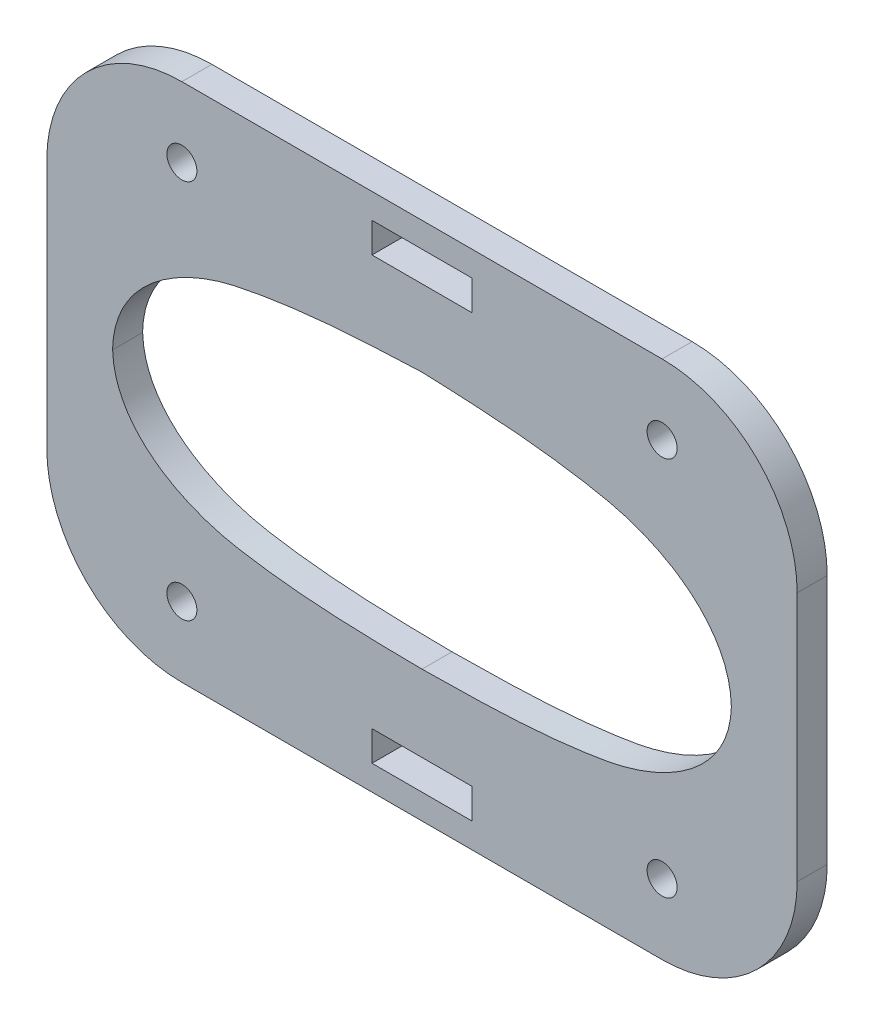
SolidWorks part; units mm, degrees
material "MDF"
ref_plane "Plano frontal" through (0, 0, 0) normal (0, 0, 1) x (1, 0, 0)
ref_plane "Plano superior" through (0, 0, 0) normal (0, 1, 0) x (1, 0, 0)
ref_plane "Plano direito" through (0, 0, 0) normal (1, 0, 0) x (0, 0, -1)
sketch "Esboço1" plane through (0, 0, 0) normal (0, 0, 1) x (1, 0, 0)
  line L0 (37.5, 0.6746) -> (-37.5, 0.6746) construction
  line L5 (24, 26.6746) -> (-24, 26.6746)
  line L6 (37.5, 13.1746) -> (37.5, -11.8254)
  line L7 (24, -25.3254) -> (-24, -25.3254)
  line L8 (-37.5, 13.1746) -> (-37.5, -11.8254)
  line L13 (37.5, 26.6746) -> (-37.5, -25.3254) construction
  line L14 (37.5, -25.3254) -> (-37.5, 26.6746) construction
  line L27 (0, -12.1787) -> (0, 13.528) construction
  line L28 (30.9233, 0) -> (-30.9233, 0) construction
  line L29 (5, -22.8254) -> (-5, -22.8254)
  line L30 (5, -22.8254) -> (5, -19.8254)
  line L31 (5, -19.8254) -> (-5, -19.8254)
  line L32 (-5, -22.8254) -> (-5, -19.8254)
  line L33 (5, -22.8254) -> (-5, -19.8254) construction
  line L34 (5, -19.8254) -> (-5, -22.8254) construction
  line L35 (5, 21.1746) -> (-5, 24.1746) construction
  line L36 (5, 24.1746) -> (-5, 21.1746) construction
  line L37 (-5, 24.1746) -> (-5, 21.1746)
  line L38 (5, 21.1746) -> (-5, 21.1746)
  line L39 (5, 24.1746) -> (5, 21.1746)
  line L40 (5, 24.1746) -> (-5, 24.1746)
  line L41 (24, -25.3254) -> (24, 26.6746) construction
  line L42 (0, -25.3254) -> (0, 26.6746) construction
  arc A0 (-24, -25.3254) -> (-37.5, -11.8254) centre (-24, -11.8254) cw
  arc A1 (-24, 26.6746) -> (-37.5, 13.1746) centre (-24, 13.1746) ccw
  arc A2 (24, 26.6746) -> (37.5, 13.1746) centre (24, 13.1746) cw
  arc A3 (37.5, -11.8254) -> (24, -25.3254) centre (24, -11.8254) cw
  circle A4 centre (24, -18.3254) radius 1.5
  circle A5 centre (-24, -18.3254) radius 1.5
  circle A6 centre (24, 19.6746) radius 1.5
  circle A7 centre (-24, 19.6746) radius 1.5
  spline S0 degree 3 poles (0, 13.528) (-6.2445, 13.2882) (-12.519, 12.9674) (-24.7294, 10.3516) (-30.8289, 6.2917) (-30.9233, 0) knots 0 0 0 0 0.5 0.5 1 1 1 1
  spline S1 degree 3 poles (30.9233, 0) (30.7402, -6.1814) (24.461, -9.8549) (12.3346, -11.9845) (6.1556, -12.1121) (0, -12.1787) knots 0 0 0 0 0.5 0.5 1 1 1 1
  spline S2 degree 3 poles (0, 13.528) (6.2445, 13.2882) (12.519, 12.9674) (24.7294, 10.3516) (30.8289, 6.2917) (30.9233, 0) knots 0 0 0 0 0.5 0.5 1 1 1 1
  spline S3 degree 3 poles (-30.9233, 0) (-30.7402, -6.1814) (-24.461, -9.8549) (-12.3346, -11.9845) (-6.1556, -12.1121) (0, -12.1787) knots 0 0 0 0 0.5 0.5 1 1 1 1
  point P0 (0, 0)
  point P1 (0, 0.6746)
  point P6 (0, -21.3254)
  point P18 (0, 22.6746)
  point P45 (0, 0)
  dimension "D6" = 13.5
  dimension "D8" = 3
  dimension "D9" = 7
  dimension "D1" = 52
  dimension "D2" = 75
  dimension "D3" = 10
  dimension "D4" = 3
  dimension "D7" = 4
extrude "Ressalto-extrusão1" add sketch "Esboço1" along normal blind 3
